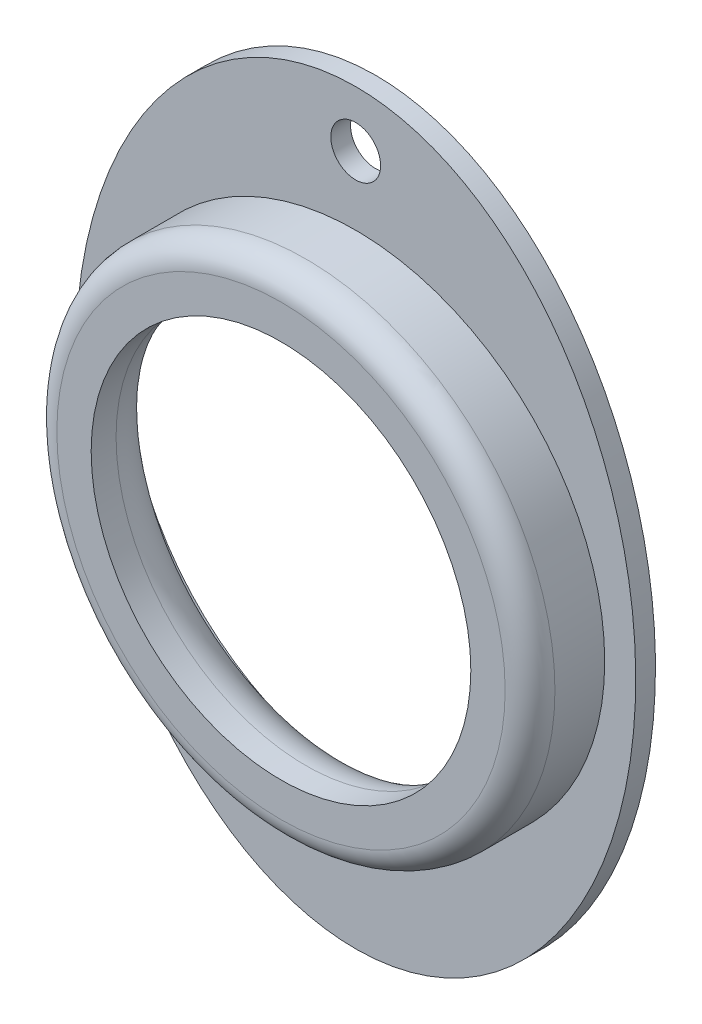
SolidWorks part; units mm, degrees
ref_plane "Front Plane" through (0, 0, 0) normal (0, 0, 1) x (1, 0, 0)
ref_plane "Top Plane" through (0, 0, 0) normal (0, 1, 0) x (1, 0, 0)
ref_plane "Right Plane" through (0, 0, 0) normal (1, 0, 0) x (0, 0, -1)
sketch "Sketch1" plane through (0, 0, 0) normal (0, 0, 1) x (1, 0, 0)
  circle A0 centre (0, 0) radius 15.251
  circle A1 centre (0, 0) radius 20.0083
  ellipse E0 centre (0, 0) end of major axis (0, 30) minor radius 22.5
  point P15 (0.0846, 20.5962)
  dimension "D2" = 60
  dimension "D4" = 40.0166
  dimension "D5" = 0.0846
  dimension "D3" = 30.502
  dimension "D1" = 45
  dimension "D6" = 20.5962
extrude "Boss-Extrude1" add sketch "Sketch1" against normal blind 1.5875 contours E0 A1 region at (0.0075, -29.25, 0)
extrude "Boss-Extrude2" add sketch "Sketch1<3>" along normal blind 6 separate body contours A1 A0 region at (-19.4424, 0, 0)
sketch "Sketch1<3>" plane through (0, 0, 0) normal (0, 0, 1) x (1, 0, 0) same geometry as "Sketch1"
fillet "Fillet1" radius 4 1 edges at (15.251, 0, 0)
fillet "Fillet2" radius 2 1 edges at (20.0083, 0, 6)
sketch "Sketch3" plane through (0, 0, -1.5875) normal (0, 0, -1) x (-1, 0, 0)
  line L0 (0, 30) -> (0, 25.5) construction
  circle A0 centre (0, 25.5) radius 2
  ellipse E0 centre (0, 0) end of major axis (0, 30) minor radius 22.5 construction
  dimension "D2" = 4
  dimension "D1" = 4.5
extrude "Cut-Extrude1" cut sketch "Sketch3" against normal through all both
